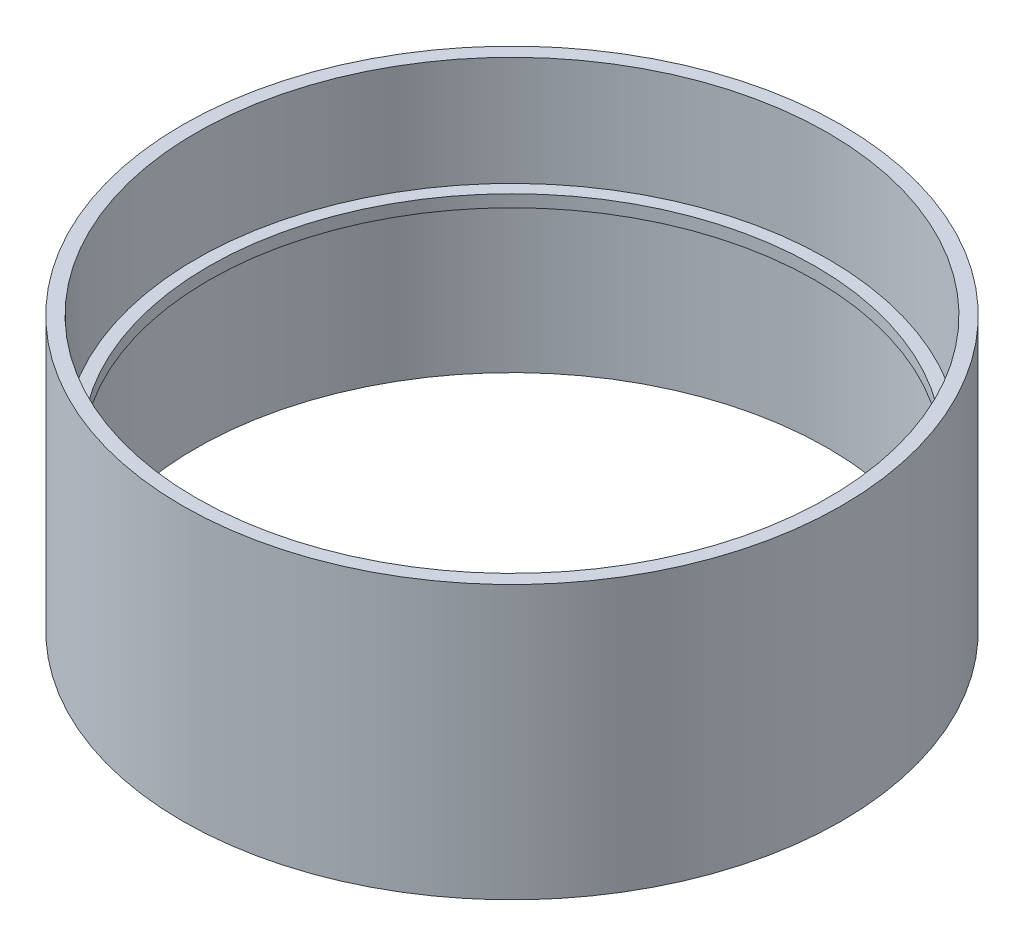
SolidWorks part; units mm, degrees
ref_plane "Front Plane" through (0, 0, 0) normal (0, 0, 1) x (1, 0, 0)
ref_plane "Top Plane" through (0, 0, 0) normal (0, 1, 0) x (1, 0, 0)
ref_plane "Right Plane" through (0, 0, 0) normal (1, 0, 0) x (0, 0, -1)
sketch "Sketch2" plane through (0, 0, 0) normal (0, 0, 1) x (1, 0, 0)
  line L0 (0, 0) -> (0, 38.3887) construction
  line L1 (39.6875, 0) -> (39.6875, 19.05)
  line L2 (39.6875, 19.05) -> (38.1, 19.05)
  line L3 (38.1, 19.05) -> (38.1, 20.574)
  line L4 (38.1, 20.574) -> (39.6875, 20.574)
  line L5 (39.6875, 20.574) -> (39.6875, 34.29)
  line L6 (39.6875, 34.29) -> (41.402, 34.29)
  line L7 (41.402, 34.29) -> (41.402, 0)
  line L8 (41.402, 0) -> (39.6875, 0)
  point P9 (0, 0)
  point P12 (0, 38.3887)
  dimension "D1" = 1.524
  dimension "D2" = 79.375
  dimension "D3" = 82.804
  dimension "D4" = 19.05
  dimension "D5" = 34.29
  dimension "D6" = 76.2
revolve "Revolve1" add sketch "Sketch2" angle 360 about L0
